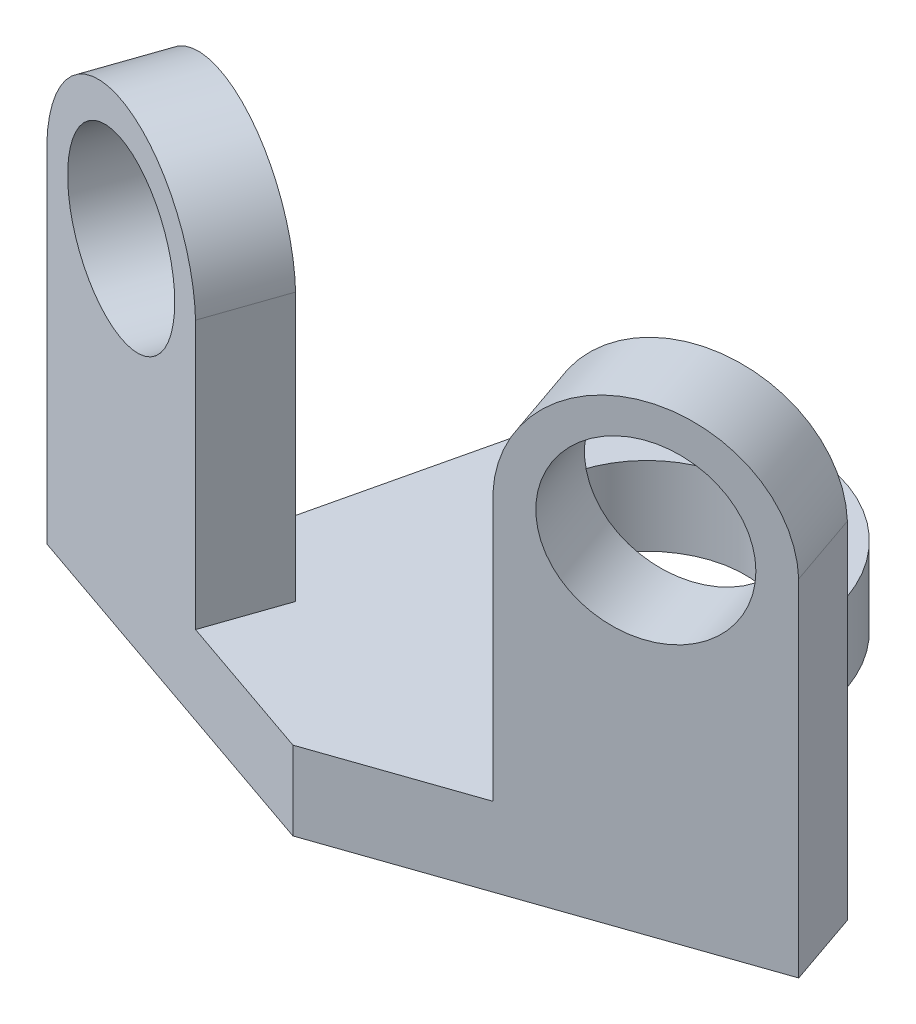
SolidWorks part; units mm, degrees
ref_plane "Front Plane" through (0, 0, 0) normal (0, 0, 1) x (1, 0, 0)
ref_plane "Top Plane" through (0, 0, 0) normal (0, 1, 0) x (1, 0, 0)
ref_plane "Right Plane" through (0, 0, 0) normal (1, 0, 0) x (0, 0, -1)
sketch "Sketch2" plane through (0, 0, 0) normal (0, 1, 0) x (1, 0, 0)
  line L0 (-19.474, 4.5567) -> (-26.4556, -25.2805)
  line L1 (19.474, 4.5567) -> (26.4556, -25.2805)
  line L3 (0, -45) -> (47.7931, -28.489)
  line L4 (18.9037, -38.4694) -> (15.6384, -29.0175)
  line L5 (15.6384, -29.0175) -> (44.5278, -19.0372)
  line L6 (44.5278, -19.0372) -> (47.7931, -28.489)
  line L7 (0, 25.9673) -> (0, -49.3194) construction
  line L8 (-44.5278, -19.0372) -> (-47.7931, -28.489)
  line L9 (0, -45) -> (-47.7931, -28.489)
  line L10 (-18.9037, -38.4694) -> (-15.6384, -29.0175)
  line L11 (-15.6384, -29.0175) -> (-44.5278, -19.0372)
  circle A0 centre (0, 0) radius 12.5
  arc A1 (19.474, 4.5567) -> (-19.474, 4.5567) centre (0, 0) ccw
  dimension "D1" = 25
  dimension "D2" = 40
  dimension "D3" = 45
  dimension "D4" = 20
  dimension "D5" = 10
  dimension "D6" = 10
  dimension "D7" = 218.117
extrude "Boss-Extrude1" add sketch "Sketch2" along normal blind 10 contours L7 A1 L0 L11 L10 L9 A0 | A1 L7 A0 L3 L4 L5 L1 | L6 L5 L4 L3 | L10 L11 L8 L9 region at (-11.4206, 0, 15.84) region at (-31.7158, 0, 28.7533) region at (11.4206, 0, 15.84) region at (31.7158, 0, 28.7533)
sketch "Sketch6" plane through (0, 10, 0) normal (0, 1, 0) x (1, 0, 0)
  line L0 (47.7931, -28.489) -> (44.5278, -19.0372)
  line L1 (44.5278, -19.0372) -> (15.6384, -29.0175)
  line L2 (15.6384, -29.0175) -> (18.9037, -38.4694)
  line L3 (0, -45) -> (47.7931, -28.489) construction
  line L4 (18.9037, -38.4694) -> (47.7931, -28.489)
  line L5 (0, 22.1983) -> (0, -52.0737) construction
  line L6 (-47.7931, -28.489) -> (-44.5278, -19.0372)
  line L7 (-18.9037, -38.4694) -> (-47.7931, -28.489)
  line L8 (-15.6384, -29.0175) -> (-18.9037, -38.4694)
  line L9 (-44.5278, -19.0372) -> (-15.6384, -29.0175)
  dimension "D1" = 20
extrude "Boss-Extrude3" add sketch "Sketch6" along normal blind 50
sketch "Sketch5" plane through (-13.8885, 0, 40.202) normal (-0.3265, 0, 0.9452) x (0.9452, 0, 0.3265)
  line L1 (14.9638, -2.3419) -> (12.8412, 66.3587) construction
sketch "Sketch7" plane through (-13.8885, 0, 40.202) normal (-0.3265, 0, 0.9452) x (0.9452, 0, 0.3265)
  line L0 (-20.5885, 60) -> (-20.5885, 0) construction
  line L1 (-35.8708, 60) -> (-5.3061, 60) construction
  line L2 (14.6939, 0) -> (-35.8708, 0) construction
  line L3 (-35.8885, 43.3322) -> (-35.8708, 60)
  line L4 (-35.8708, 60) -> (-5.3061, 60)
  line L5 (-5.3061, 60) -> (-5.2885, 43.3322)
  arc A1 (-5.2885, 43.3322) -> (-35.8885, 43.3322) centre (-20.5885, 43.3322) ccw
  dimension "D1" = 30.6
  dimension "D2" = 15.3
extrude "Cut-Extrude2" cut sketch "Sketch7" against normal blind 50 contours A1 L3 L4 L5
sketch "Sketch8" plane through (13.8885, 0, 40.202) normal (0.3265, 0, 0.9452) x (0.9452, 0, -0.3265)
  line L0 (20.5885, 60) -> (20.5885, 0) construction
  line L1 (5.3061, 60) -> (35.8708, 60) construction
  line L2 (-14.6939, 0) -> (35.8708, 0) construction
  line L3 (-35.5312, 45.0736) -> (5.2985, 43.4534) construction
  line L4 (5.2985, 43.4534) -> (-35.5312, 45.0736) construction
  line L5 (5.2985, 43.4534) -> (5.3061, 60)
  line L6 (5.3061, 60) -> (35.8708, 60)
  line L7 (35.8708, 60) -> (35.8785, 43.4534)
  arc A0 (35.8785, 43.4534) -> (5.2985, 43.4534) centre (20.5885, 43.4534) ccw
  dimension "D1" = 30.58
extrude "Cut-Extrude3" cut sketch "Sketch8" against normal blind 50
sketch "Sketch9" plane through (-13.8885, 0, 40.202) normal (-0.3265, 0, 0.9452) x (0.9452, 0, 0.3265)
  circle A0 centre (-20.5885, 43.3322) radius 11
  dimension "D1" = 22
extrude "Cut-Extrude4" cut sketch "Sketch9" against normal blind 10
sketch "Sketch10" plane through (13.8885, 0, 40.202) normal (0.3265, 0, 0.9452) x (0.9452, 0, -0.3265)
  circle A0 centre (20.5885, 43.4534) radius 11
  dimension "D1" = 22
extrude "Cut-Extrude5" cut sketch "Sketch10" against normal blind 10
